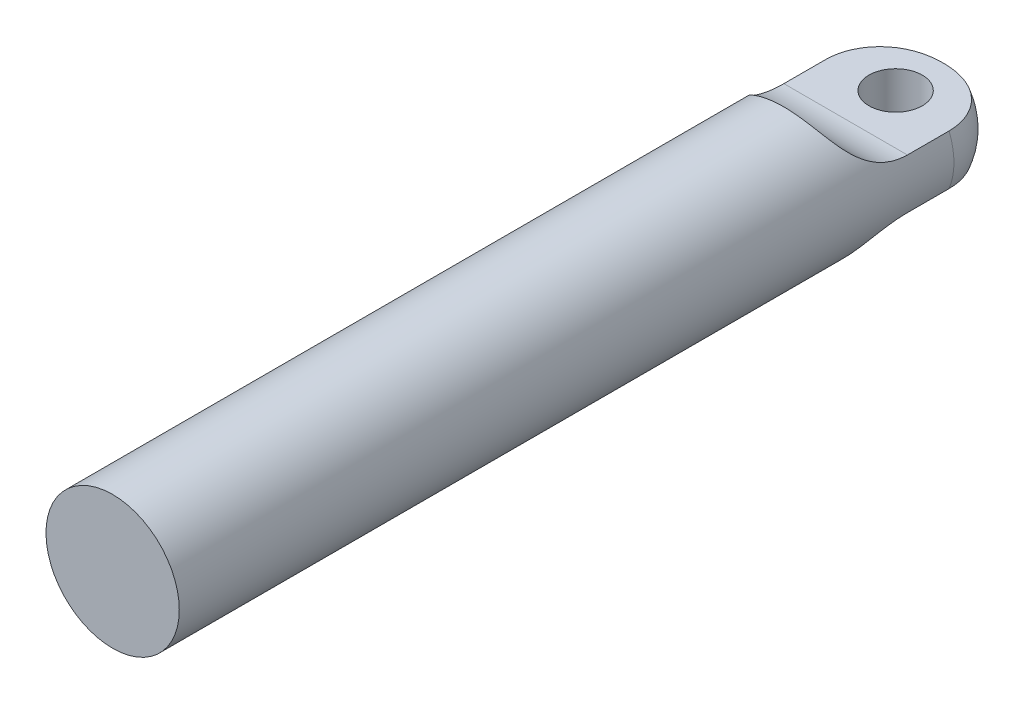
SolidWorks part; units mm, degrees
material "6061 Alloy"
ref_plane "Front Plane" through (0, 0, 0) normal (0, 0, 1) x (1, 0, 0)
ref_plane "Top Plane" through (0, 0, 0) normal (0, 1, 0) x (1, 0, 0)
ref_plane "Right Plane" through (0, 0, 0) normal (1, 0, 0) x (0, 0, -1)
sketch "Sketch1" plane through (0, 0, 0) normal (0, 0, 1) x (1, 0, 0)
  circle A0 centre (0, 0) radius 4
  dimension "D1" = 8
extrude "Boss-Extrude1" add sketch "Sketch1" along normal mid plane 50
sketch "Sketch2" plane through (0, 0, 0) normal (1, 0, 0) x (0, 0, -1)
  line L0 (0, 0) -> (25, 0) construction
  line L1 (25, -4) -> (25, 4) construction
  line L2 (15, -4) -> (15, -1.5)
  line L3 (25, 4) -> (15, 4)
  line L4 (25, 4) -> (25, 1.5)
  line L5 (25, 1.5) -> (15, 1.5)
  line L6 (15, 4) -> (15, 1.5)
  line L7 (25, -1.5) -> (15, -1.5)
  line L8 (25, -4) -> (25, -1.5)
  line L9 (25, -4) -> (15, -4)
  dimension "D1" = 3
  dimension "D2" = 10
extrude "Cut-Extrude1" cut sketch "Sketch2" against normal through all both and the other way through all
fillet "Fillet1" radius 4 2 edges at (0, -1.5, -15) (0, 1.5, -15)
hole_wizard "M3 Clearance Hole1" positions "Sketch5" profile "Sketch6" hole size "M3" standard "ANSI Metric" end condition through all
sketch "Sketch5" plane through (0, 1.5, 0) normal (0, 1, 0) x (1, 0, 0)
  line L0 (0, 25) -> (0, 19) construction
  line L1 (-3.7081, 25) -> (3.7081, 25) construction
  line L2 (-3.7081, 19) -> (3.7081, 19) construction
  point P0 (0, 22)
  point P11 (0, 0)
sketch "Sketch6" plane through (0, 1.5, -22) normal (1, 0, 0) x (0, 0, 1)
  line L0 (0, 0) -> (0, 5.5)
  line L1 (0, 5.5) -> (1.6, 5.5)
  line L2 (1.6, 5.5) -> (1.6, 0)
  line L5 (1.6, 0) -> (0, 0)
  line L11 (0, -6.35) -> (0, 107.95) construction
  dimension "Thru Hole Dia." = 3.2
  dimension "Thru Hole Depth" = 5.5
fillet "Fillet2" radius 3.5 1 edges at (4, 0, -25)
